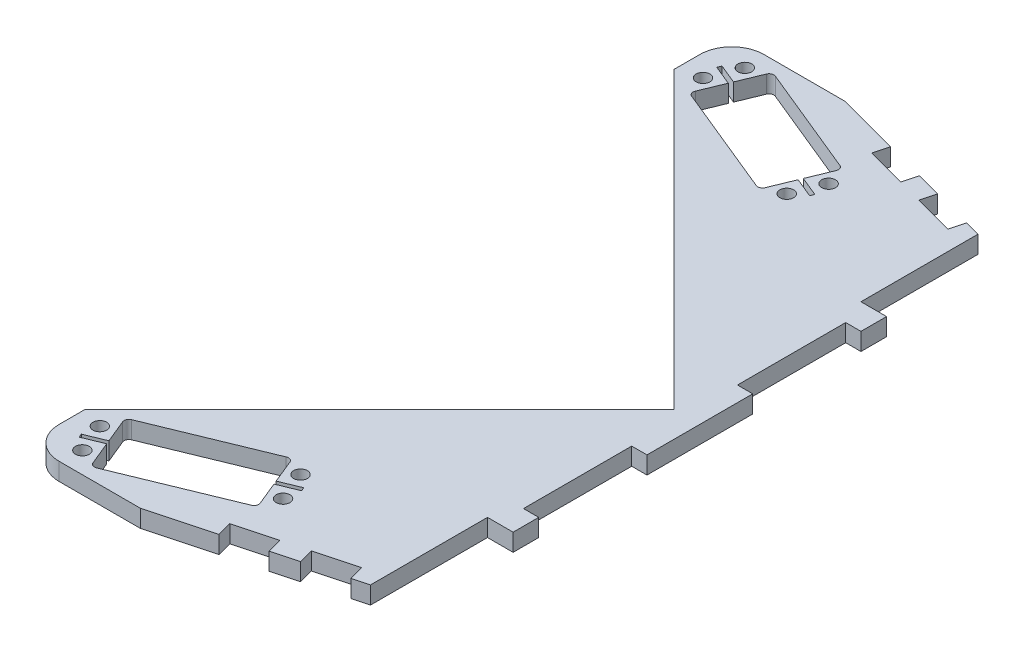
SolidWorks part; units mm, degrees
ref_plane "Front" through (0, 0, 0) normal (0, 0, 1) x (1, 0, 0)
ref_plane "Top" through (0, 0, 0) normal (0, 1, 0) x (1, 0, 0)
ref_plane "Right" through (0, 0, 0) normal (1, 0, 0) x (0, 0, -1)
ref_axis "side-side" through (80.9, 0, 0) along (-1, 0, 0)
ref_axis "up-down" through (0, 50, 0) along (0, -1, 0)
ref_axis "front-back" through (0, 0, -80.9) along (0, 0, 1)
sketch "Sketch1" plane through (0, 0, 0) normal (0, 1, 0) x (1, 0, 0)
  line L0 (-82.7905, 89.3902) -> (-79.7972, 96.6741)
  line L1 (0, 0) -> (-92, 92)
  line L2 (-92, 92) -> (-92, 110)
  line L3 (-79.322, 97.8303) -> (-76.3287, 105.1142)
  line L4 (-79.322, 97.8303) -> (-76.3287, 105.1142)
  line L5 (-92, 110) -> (-56.6019, 110)
  line L6 (8, 58.293) -> (8, -58.293)
  line L7 (0, 0) -> (58.8362, 0) construction
  line L8 (-92, -110) -> (-56.6019, -110)
  line L9 (-92, -110) -> (-92, -92)
  line L10 (0, 0) -> (-92, -92)
  line L11 (-82.7905, 89.3902) -> (-79.7972, 96.6741)
  line L12 (-42.3244, 82.6259) -> (-42.7995, 81.4697)
  line L13 (-42.7995, 81.4697) -> (-36.6949, 78.961)
  line L14 (-36.6949, 78.961) -> (-36.2198, 80.1172)
  line L15 (-36.2198, 80.1172) -> (-42.3244, 82.6259)
  line L16 (-56.6019, 110) -> (0, 94.8336)
  line L17 (-42.7995, 81.4697) -> (-36.6949, 78.961)
  line L18 (-36.6949, 78.961) -> (-36.2198, 80.1172)
  line L19 (-36.2198, 80.1172) -> (-42.3244, 82.6259)
  line L20 (-85.4267, 100.339) -> (-85.9018, 99.1828)
  line L21 (-85.9018, 99.1828) -> (-79.7972, 96.6741)
  line L22 (-79.7972, 96.6741) -> (-79.322, 97.8303)
  line L23 (-79.322, 97.8303) -> (-85.4267, 100.339)
  line L24 (-85.4267, 100.339) -> (-85.9018, 99.1828)
  line L25 (-85.9018, 99.1828) -> (-79.7972, 96.6741)
  line L26 (0, -94.8336) -> (-56.6019, -110)
  line L27 (-79.322, 97.8303) -> (-85.4267, 100.339)
  line L28 (-40.1483, 91.8674) -> (-74.3711, 105.9314)
  line L29 (-40.1483, 91.8674) -> (-74.3711, 105.9314)
  line L30 (-39.331, 89.9098) -> (-42.3244, 82.6259)
  line L31 (-42.7995, 81.4697) -> (-45.7929, 74.1858)
  line L32 (-42.7995, 81.4697) -> (-45.7929, 74.1858)
  line L33 (-39.331, 89.9098) -> (-42.3244, 82.6259)
  line L34 (-47.7504, 73.3685) -> (-81.9733, 87.4326)
  line L35 (-47.7504, 73.3685) -> (-81.9733, 87.4326)
  line L36 (-47.7504, -73.3685) -> (-81.9733, -87.4326)
  line L37 (-39.331, -89.9098) -> (-42.3244, -82.6259)
  line L38 (-42.7995, -81.4697) -> (-45.7929, -74.1858)
  line L39 (-40.1483, -91.8674) -> (-74.3711, -105.9314)
  line L40 (-79.322, -97.8303) -> (-85.4267, -100.339)
  line L41 (-85.9018, -99.1828) -> (-79.7972, -96.6741)
  line L42 (-85.4267, -100.339) -> (-85.9018, -99.1828)
  line L43 (-36.2198, -80.1172) -> (-42.3244, -82.6259)
  line L44 (-36.6949, -78.961) -> (-36.2198, -80.1172)
  line L45 (-42.7995, -81.4697) -> (-36.6949, -78.961)
  line L46 (-82.7905, -89.3902) -> (-79.7972, -96.6741)
  line L47 (-79.322, -97.8303) -> (-76.3287, -105.1142)
  line L50 (0, 94.8336) -> (0, 58.293)
  line L51 (0, 58.293) -> (8, 58.293)
  line L52 (0, -94.8336) -> (0, -58.293)
  line L53 (0, -58.293) -> (8, -58.293)
  arc A0 (-87.2208, 93.5353) -> (-86.1945, 96.0326) centre (-85.1599, 94.1479) ccw construction
  circle A1 centre (-85.1599, 94.1479) radius 2.15
  arc A2 (-83.4197, 102.7847) -> (-82.3934, 105.282) centre (-81.3588, 103.3973) ccw construction
  circle A3 centre (-81.3588, 103.3973) radius 2.15
  arc A4 (-34.9008, 85.7647) -> (-35.9271, 83.2673) centre (-36.9616, 85.1521) ccw construction
  circle A5 centre (-36.9616, 85.1521) radius 2.15
  arc A6 (-38.7018, 76.5153) -> (-39.7281, 74.0179) centre (-40.7627, 75.9026) ccw construction
  circle A7 centre (-40.7627, 75.9026) radius 2.15
  arc A8 (-74.3711, 105.9314) -> (-75.7356, 105.8164) centre (-74.9413, 104.544) ccw
  arc A9 (-75.7356, 105.8164) -> (-76.3287, 105.1142) centre (-74.9413, 104.544) ccw
  arc A10 (-75.7356, 105.8164) -> (-76.3287, 105.1142) centre (-74.9413, 104.544) ccw
  arc A11 (-74.3711, 105.9314) -> (-75.7356, 105.8164) centre (-74.9413, 104.544) ccw
  arc A12 (-82.7905, 89.3902) -> (-82.8626, 88.4738) centre (-81.4031, 88.82) ccw
  arc A13 (-82.8626, 88.4738) -> (-81.9733, 87.4326) centre (-81.4031, 88.82) ccw
  arc A14 (-82.8626, 88.4738) -> (-81.9733, 87.4326) centre (-81.4031, 88.82) ccw
  arc A15 (-82.7905, 89.3902) -> (-82.8626, 88.4738) centre (-81.4031, 88.82) ccw
  arc A16 (-39.331, 89.9098) -> (-39.2589, 90.8262) centre (-40.7184, 90.48) ccw
  arc A17 (-39.2589, 90.8262) -> (-40.1483, 91.8674) centre (-40.7184, 90.48) ccw
  arc A18 (-39.2589, 90.8262) -> (-40.1483, 91.8674) centre (-40.7184, 90.48) ccw
  arc A19 (-39.331, 89.9098) -> (-39.2589, 90.8262) centre (-40.7184, 90.48) ccw
  arc A20 (-46.386, 73.4835) -> (-45.7929, 74.1858) centre (-47.1803, 74.756) ccw
  arc A21 (-47.7504, 73.3685) -> (-46.386, 73.4835) centre (-47.1803, 74.756) ccw
  arc A22 (-47.7504, 73.3685) -> (-46.386, 73.4835) centre (-47.1803, 74.756) ccw
  arc A23 (-46.386, 73.4835) -> (-45.7929, 74.1858) centre (-47.1803, 74.756) ccw
  arc A24 (-46.386, -73.4835) -> (-45.7929, -74.1858) centre (-47.1803, -74.756) cw
  arc A25 (-47.7504, -73.3685) -> (-46.386, -73.4835) centre (-47.1803, -74.756) cw
  arc A26 (-39.331, -89.9098) -> (-39.2589, -90.8262) centre (-40.7184, -90.48) cw
  arc A27 (-39.2589, -90.8262) -> (-40.1483, -91.8674) centre (-40.7184, -90.48) cw
  arc A28 (-82.7905, -89.3902) -> (-82.8626, -88.4738) centre (-81.4031, -88.82) cw
  arc A29 (-82.8626, -88.4738) -> (-81.9733, -87.4326) centre (-81.4031, -88.82) cw
  arc A30 (-74.3711, -105.9314) -> (-75.7356, -105.8164) centre (-74.9413, -104.544) cw
  arc A31 (-75.7356, -105.8164) -> (-76.3287, -105.1142) centre (-74.9413, -104.544) cw
  circle A32 centre (-40.7627, -75.9026) radius 2.15
  circle A33 centre (-36.9616, -85.1521) radius 2.15
  circle A34 centre (-81.3588, -103.3973) radius 2.15
  circle A35 centre (-85.1599, -94.1479) radius 2.15
  dimension "D1" = 45
  dimension "D2" = 110
  dimension "D3" = 8
  dimension "D4" = 100
  dimension "D7" = 75
  dimension "D8" = 13.2562
  dimension "D9" = 64.6019
  dimension "D10" = 8
  dimension "D11" = 116.586
  dimension "D5" = 0
  dimension "D6" = 0
extrude "Boss-Extrude1" add sketch "Sketch1" along normal blind 5.461
fillet "Fillet1" radius 10 2 edges at (-92, 2.7305, 110) (-92, 2.7305, -110)
sketch "Sketch2" plane through (0, 0, 0) normal (0, 1, 0) x (1, 0, 0)
  line L4 (-4.8296, 96.1276) -> (-17.1928, 99.4404)
  line L5 (-6.0623, 91.5274) -> (-4.8296, 96.1276)
  line L6 (-18.4255, 94.8401) -> (-6.0623, 91.5274)
  line L7 (-17.1928, 99.4404) -> (-18.4255, 94.8401)
  line L8 (-4.8296, 96.1276) -> (-17.1928, 99.4404)
  line L9 (-6.0623, 91.5274) -> (-4.8296, 96.1276)
  line L10 (-18.4255, 94.8401) -> (-6.0623, 91.5274)
  line L11 (-17.1928, 99.4404) -> (-18.4255, 94.8401)
  line L12 (-24.9202, 101.5109) -> (-37.2834, 104.8236)
  line L13 (-26.1529, 96.9107) -> (-24.9202, 101.5109)
  line L14 (-38.5161, 100.2234) -> (-26.1529, 96.9107)
  line L15 (-37.2834, 104.8236) -> (-38.5161, 100.2234)
  line L16 (-24.9202, 101.5109) -> (-37.2834, 104.8236)
  line L17 (-26.1529, 96.9107) -> (-24.9202, 101.5109)
  line L18 (-38.5161, 100.2234) -> (-26.1529, 96.9107)
  line L19 (-37.2834, 104.8236) -> (-38.5161, 100.2234)
  line L20 (-26.1529, -96.9107) -> (-38.5161, -100.2234)
  line L21 (-24.9202, -101.5109) -> (-26.1529, -96.9107)
  line L22 (-37.2834, -104.8236) -> (-24.9202, -101.5109)
  line L23 (-38.5161, -100.2234) -> (-37.2834, -104.8236)
  line L24 (-26.1529, -96.9107) -> (-38.5161, -100.2234)
  line L25 (-24.9202, -101.5109) -> (-26.1529, -96.9107)
  line L26 (-37.2834, -104.8236) -> (-24.9202, -101.5109)
  line L27 (-38.5161, -100.2234) -> (-37.2834, -104.8236)
  line L28 (-6.0623, -91.5274) -> (-18.4255, -94.8401)
  line L29 (-4.8296, -96.1276) -> (-6.0623, -91.5274)
  line L30 (-17.1928, -99.4404) -> (-4.8296, -96.1276)
  line L31 (-18.4255, -94.8401) -> (-17.1928, -99.4404)
  line L32 (-6.0623, -91.5274) -> (-18.4255, -94.8401)
  line L33 (-4.8296, -96.1276) -> (-6.0623, -91.5274)
  line L34 (-17.1928, -99.4404) -> (-4.8296, -96.1276)
  line L35 (-18.4255, -94.8401) -> (-17.1928, -99.4404)
  line L64 (8, 50.293) -> (3.2375, 50.293) construction
  line L65 (3.2375, 50.293) -> (3.2375, 16.51) construction
  line L66 (8, 50.293) -> (8, 16.51) construction
  line L67 (8, 16.51) -> (3.2375, 16.51) construction
  line L68 (8, -16.51) -> (3.2375, -16.51) construction
  line L69 (8, -50.293) -> (8, -16.51) construction
  line L70 (8, -50.293) -> (3.2375, -50.293) construction
  line L71 (3.2375, -50.293) -> (3.2375, -16.51) construction
  line L72 (8, 50.293) -> (3.2375, 50.293)
  line L73 (3.2375, 50.293) -> (3.2375, 16.51)
  line L74 (8, 50.293) -> (8, 16.51)
  line L75 (8, 16.51) -> (3.2375, 16.51)
  line L76 (8, -16.51) -> (3.2375, -16.51)
  line L77 (8, -50.293) -> (8, -16.51)
  line L78 (8, -50.293) -> (3.2375, -50.293)
  line L79 (3.2375, -50.293) -> (3.2375, -16.51)
  dimension "D1" = 0
  dimension "D2" = 0
  dimension "D3" = 0
  dimension "D4" = 0
extrude "Cut-Extrude1" cut sketch "Sketch2" along normal blind 10
